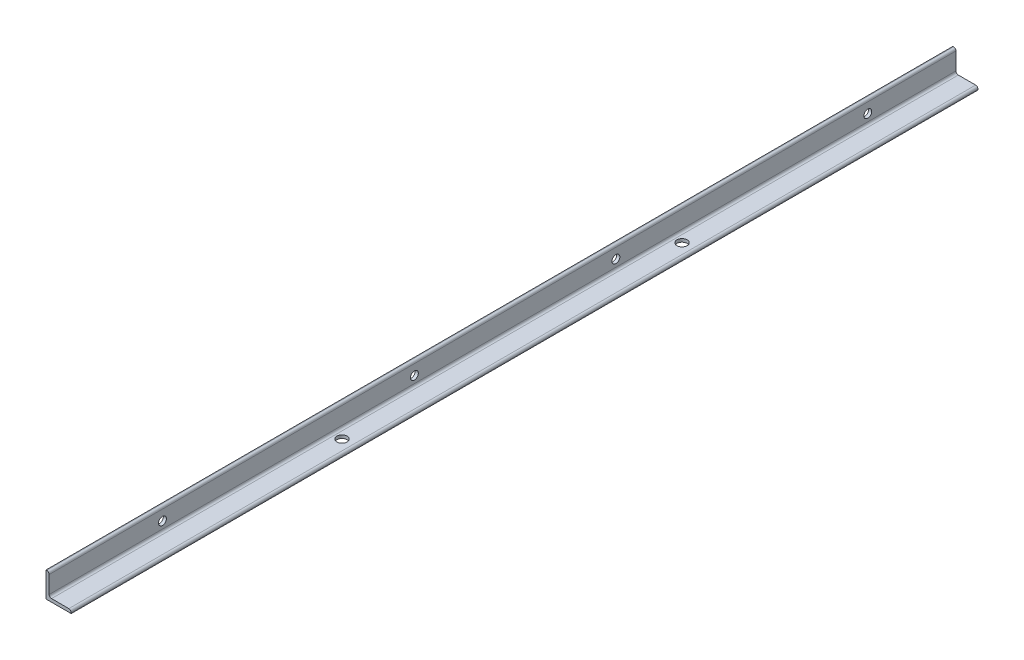
SolidWorks part; units mm, degrees
ref_plane "Front Plane" through (0, 0, 0) normal (0, 0, 1) x (1, 0, 0)
ref_plane "Top Plane" through (0, 0, 0) normal (0, 1, 0) x (1, 0, 0)
ref_plane "Right Plane" through (0, 0, 0) normal (1, 0, 0) x (0, 0, -1)
sketch "Sketch1" plane through (0, 0, 0) normal (0, 0, 1) x (1, 0, 0)
  line L0 (0, 0) -> (0, 50.8)
  line L1 (0, 50.8) -> (1.5926, 50.8)
  line L2 (6.35, 46.0426) -> (6.35, 11.1125)
  line L3 (11.1125, 6.35) -> (46.0426, 6.35)
  line L4 (50.8, 1.5926) -> (50.8, 0)
  line L5 (50.8, 0) -> (0, 0)
  arc A0 (50.8, 1.5926) -> (46.0426, 6.35) centre (46.0426, 1.5926) ccw
  arc A1 (1.5926, 50.8) -> (6.35, 46.0426) centre (1.5926, 46.0426) cw
  arc A2 (11.1125, 6.35) -> (6.35, 11.1125) centre (11.1125, 11.1125) cw
  circle A3 centre (0, 0) radius 4.7625 construction
  dimension "D2" = 1.5926
  dimension "Radius_1" = 4.7625
  dimension "Radius_2" = 4.7625
  dimension "D1" = 6.35
  dimension "V_leg" = 50.8
  dimension "H_leg" = 50.8
  dimension "Thickness" = 6.35
  dimension "Flat_wid" = 1.5926
extrude "Boss-Extrude1" add sketch "Sketch1" along normal mid plane 1828.8
hole_wizard "13/16 (0.8125) Diameter Hole1" positions "Sketch4" profile "Sketch3" hole size "13/16" standard "Ansi Inch" end condition up to next
sketch "Sketch4" plane through (0, 0, 0) normal (0, -1, 0) x (1, 0, 0)
  line L2 (25.4, -914.4) -> (25.4, 914.4) construction
  line L3 (0, 914.4) -> (50.8, 914.4) construction
  line L4 (0, -914.4) -> (50.8, -914.4) construction
  point P0 (25.4, -342.9)
  point P1 (25.4, 342.9)
  dimension "D1" = 571.5
  dimension "D2" = 571.5
sketch "Sketch3" plane through (25.4, 0, -342.9) normal (1, 0, 0) x (0, 0, -1)
  line L0 (0, 0) -> (0, 6.35)
  line L1 (0, 6.35) -> (10.3187, 6.35)
  line L2 (10.3187, 6.35) -> (10.3187, 0)
  line L5 (10.3187, 0) -> (0, 0)
  line L11 (0, -6.35) -> (0, 107.95) construction
  dimension "Thru Hole Dia." = 20.6375
  dimension "Thru Hole Depth" = 6.35
hole_wizard "5/8 (0.625) Diameter Hole1" positions "Sketch6" profile "Sketch5" hole size "5/8" standard "Ansi Inch" end condition up to next
sketch "Sketch6" plane through (0, 0, 0) normal (-1, 0, 0) x (0, 0, 1)
  line L0 (-914.4, 25.4) -> (914.4, 25.4) construction
  line L3 (-914.4, 50.8) -> (-914.4, 0) construction
  line L4 (914.4, 50.8) -> (914.4, 0) construction
  point P0 (-736.6, 25.4)
  point P1 (-228.6, 25.4)
  point P3 (177.8, 25.4)
  point P5 (685.8, 25.4)
  dimension "D1" = 508
  dimension "D2" = 508
  dimension "D3" = 177.8
  dimension "D4" = 406.4
sketch "Sketch5" plane through (0, 25.4, -736.6) normal (0, 1, 0) x (0, 0, 1)
  line L0 (0, 0) -> (0, 6.35)
  line L1 (0, 6.35) -> (7.9375, 6.35)
  line L2 (7.9375, 6.35) -> (7.9375, 0)
  line L5 (7.9375, 0) -> (0, 0)
  line L11 (0, -6.35) -> (0, 107.95) construction
  dimension "Thru Hole Dia." = 15.875
  dimension "Thru Hole Depth" = 6.35
